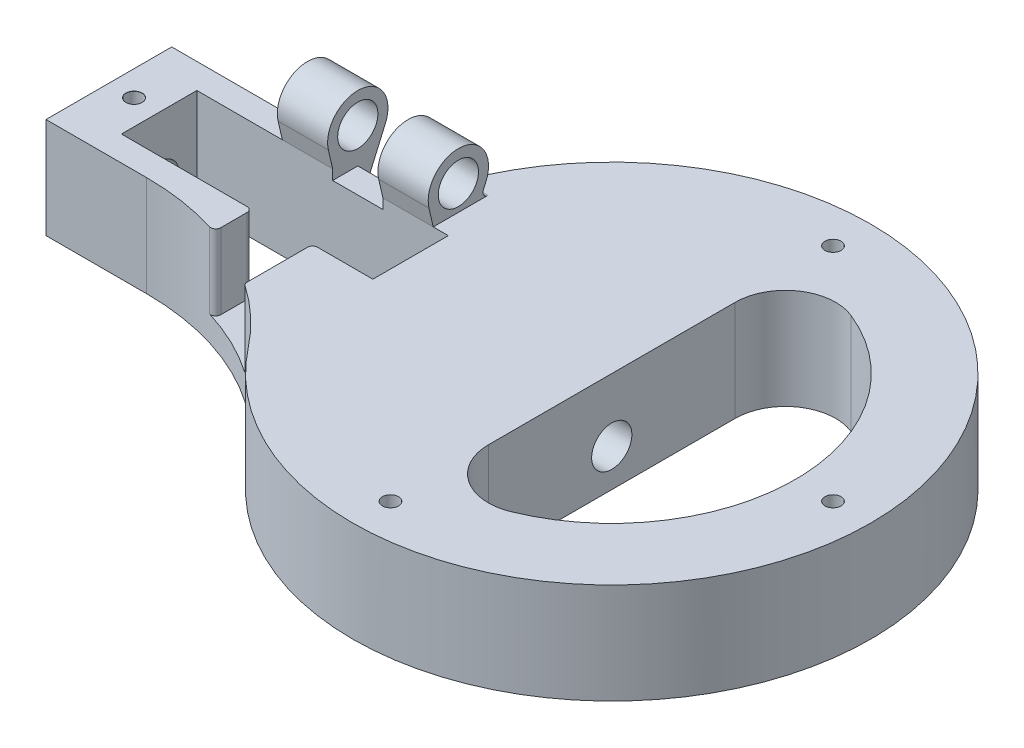
SolidWorks part; units mm, degrees
ref_plane "Front Plane" through (0, 0, 0) normal (0, 0, 1) x (1, 0, 0)
ref_plane "Top Plane" through (0, 0, 0) normal (0, 1, 0) x (1, 0, 0)
ref_plane "Right Plane" through (0, 0, 0) normal (1, 0, 0) x (0, 0, -1)
sketch "Sketch2" plane through (0, 0, 0) normal (0, 1, 0) x (1, 0, 0)
  line L1 (-20, -7.5) -> (20, -7.5)
  line L2 (-20, -7.5) -> (-20, 7.5)
  line L3 (-20, 7.5) -> (20, 7.5)
  line L4 (20, -7.5) -> (20, 7.5)
  line L5 (-20, -7.5) -> (20, 7.5) construction
  line L6 (-20, 7.5) -> (20, -7.5) construction
  line L7 (-40, -12.5) -> (60, -12.5)
  line L8 (-40, -12.5) -> (-40, 12.5)
  line L9 (-40, 12.5) -> (60, 12.5)
  line L10 (60, -12.5) -> (60, 12.5)
  point P0 (0, 0)
  point P10 (-40, 0)
  dimension "D1" = 15
  dimension "D2" = 25
  dimension "D3" = 20
  dimension "D4" = 40
  dimension "D5" = 40
extrude "Boss-Extrude1" add sketch "Sketch2" along normal blind 20
sketch "Sketch3" plane through (60, 0, 0) normal (1, 0, 0) x (0, 0, -1)
  line L0 (0, 0) -> (0, 7.5) construction
  line L1 (-12.5, 0) -> (12.5, 0) construction
  circle A0 centre (0, 7.5) radius 4
  dimension "D1" = 8
  dimension "D2" = 7.5
extrude "Cut-Extrude1" cut sketch "Sketch3" against normal up to next
sketch "Sketch4" plane through (-40, 0, 0) normal (-1, 0, 0) x (0, 0, 1)
  circle A0 centre (0, 7.5) radius 4
  dimension "D2" = 8
  dimension "D1" = 7.5
extrude "Cut-Extrude2" cut sketch "Sketch4" against normal up to next
sketch "Sketch7" plane through (0, 20, 0) normal (0, 1, 0) x (1, 0, 0)
  line L0 (-40, 12.5) -> (-40, -12.5) construction
  point P0 (-35, 0)
  dimension "D1" = 5
hole_wizard "Ø3.2 (3.2) Diameter Hole1" positions "Sketch7" profile "Sketch6" hole size "Ø3.2" standard "ANSI Metric" end condition through all
sketch "Sketch6" plane through (-35, 20, 0) normal (1, 0, 0) x (0, 0, 1)
  line L0 (0, 0) -> (0, 20)
  line L1 (0, 20) -> (1.6, 20)
  line L2 (1.6, 20) -> (1.6, 0.025)
  line L3 (1.6, 0.025) -> (1.625, 0)
  line L5 (1.625, 0) -> (0, 0)
  line L6 (-1.6, 0.025) -> (-1.625, 0) construction
  line L11 (0, -6.35) -> (0, 107.95) construction
  dimension "Thru Hole Dia." = 3.2
  dimension "Thru Hole Depth" = 20
  dimension "Near C'Sink Dia." = 3.25
  dimension "Near C'Sink Angle" = 90
sketch "Sketch9" plane through (-20, 0, 0) normal (1, 0, 0) x (0, 0, -1)
  line L0 (7.5, 20) -> (12.5, 20)
  line L1 (12.5, 20) -> (12.5, 10)
  line L4 (6.655, 23.645) -> (7.5, 20)
  line L7 (12.5, 10) -> (17.9991, 22.6)
  line L8 (12.5, 20) -> (12.5, 0) construction
  circle A0 centre (12.5, 25) radius 4
  arc A1 (17.9991, 22.6) -> (6.655, 23.645) centre (12.5, 25) ccw
  point P2 (6.8949, 19.1907)
  dimension "D1" = 8
  dimension "D4" = 6
  dimension "D2" = 5
  dimension "D3" = 10
extrude "Boss-Extrude3" add sketch "Sketch9" along normal blind 40
sketch "Sketch12" plane through (0, 0, -7.5) normal (0, 0, 1) x (1, 0, 0)
  line L0 (20, 23.645) -> (20, 20) construction
  line L1 (-20, 20) -> (-13, 20)
  line L2 (-20, 20) -> (-20, 35)
  line L3 (-20, 35) -> (-13, 35)
  line L4 (-13, 20) -> (-13, 35)
  line L5 (-3, 20) -> (7, 20)
  line L6 (-3, 20) -> (-3, 35)
  line L7 (-3, 35) -> (7, 35)
  line L8 (7, 20) -> (7, 35)
  line L9 (17, 20) -> (20, 20)
  line L10 (17, 20) -> (17, 35)
  line L11 (17, 35) -> (20, 35)
  line L12 (20, 20) -> (20, 35)
  dimension "D1" = 10
  dimension "D2" = 10
  dimension "D3" = 15
  dimension "D4" = 17
  dimension "D5" = 10
extrude "Cut-Extrude3" cut sketch "Sketch12" against normal through all both and the other way through all
sketch "Sketch11" plane through (0, 0, 0) normal (0, -1, 0) x (1, 0, 0)
  line L5 (60, 12.5) -> (60, 36.5)
  line L7 (60, 12.5) -> (10.04, 12.5)
  line L9 (60, 12.5) -> (60, -12.5) construction
  line L15 (60, -12.5) -> (60, -36.5)
  line L17 (10.04, -12.5) -> (60, -12.5)
  circle A0 centre (60, 0) radius 44 construction
  circle A1 centre (60, 44) radius 1.6
  circle A2 centre (60, -44) radius 1.6
  circle A3 centre (104, 0) radius 1.6
  arc A4 (60, -36.5) -> (60, 36.5) centre (60, 0) ccw
  arc A5 (10.04, -12.5) -> (10.04, 12.5) centre (60, 0) ccw
  dimension "D1" = 88
  dimension "D2" = 3.2
  dimension "D3" = 15
  dimension "D4" = 7.5
extrude "Boss-Extrude4" add sketch "Sketch11" against normal blind 20
fillet "Fillet1" radius 10 2 edges at (60, 10, 36.5) (60, 10, -36.5)
sketch "Sketch13" plane through (0, 20, 0) normal (0, 1, 0) x (1, 0, 0)
  line L0 (-13, 18.5) -> (-13, 6.5) construction
  line L1 (-20, 16.8644) -> (-13, 16.8644)
  line L2 (-20, 16.8644) -> (-20, 12.5)
  line L3 (-20, 12.5) -> (-13, 12.5)
  line L4 (-13, 16.8644) -> (-13, 12.5)
  line L5 (7, 16.8644) -> (7, 7.5) construction
  line L6 (-3, 16.8644) -> (7, 16.8644)
  line L7 (-3, 16.8644) -> (-3, 12.5)
  line L8 (-3, 12.5) -> (7, 12.5)
  line L9 (7, 16.8644) -> (7, 12.5)
  line L10 (-20, 12.5) -> (-40, 12.5) construction
extrude "Cut-Extrude4" cut sketch "Sketch13" against normal through all
fillet "Fillet3" radius 1 2 edges at (-8, 10, -12.5) (14.1698, 20, -16.8644)
fillet "Fillet4" radius 50 1 edges at (10.04, 10, 12.5)
sketch "Sketch14" plane through (0, 20, 0) normal (0, 1, 0) x (1, 0, 0)
  line L1 (-4, -7.5) -> (8, -7.5)
  line L2 (-4, -7.5) -> (-4, -22.5)
  line L3 (-4, -22.5) -> (8, -22.5)
  line L4 (8, -7.5) -> (8, -22.5)
  line L7 (-20, -7.5) -> (20, -7.5) construction
  line L9 (2, 7.5) -> (2, -7.5) construction
  line L10 (7, 7.5) -> (-3, 7.5) construction
  dimension "D1" = 15
  dimension "D2" = 6
extrude "Cut-Extrude5" cut sketch "Sketch14" against normal blind 15
sketch "Sketch15" plane through (0, 20, 0) normal (0, 1, 0) x (1, 0, 0)
  line L0 (-20, -7.5) -> (20, -7.5) construction
  line L1 (-20, 7.5) -> (-30, 7.5)
  line L2 (-20, 7.5) -> (-20, -7.5)
  line L3 (-20, -7.5) -> (-30, -7.5)
  line L4 (-30, 7.5) -> (-30, -7.5)
  line L5 (-40, -12.5) -> (-40, 12.5) construction
  dimension "D1" = 10
extrude "Cut-Extrude6" cut sketch "Sketch15" against normal through all
sketch "Sketch16" plane through (0, 20, 0) normal (0, 1, 0) x (1, 0, 0)
  line L1 (-3, 12.5) -> (7, 12.5)
  line L2 (-3, 12.5) -> (-3, 7.5)
  line L3 (-3, 7.5) -> (7, 7.5)
  line L4 (7, 12.5) -> (7, 7.5)
extrude "Cut-Extrude7" cut sketch "Sketch16" against normal blind 2
fillet "Fillet5" radius 1 4 edges at (8, 12.5, 7.5) (8, 12.5, 21.0585) (-4, 12.5, 15.1207) (-4, 12.5, 7.5)
